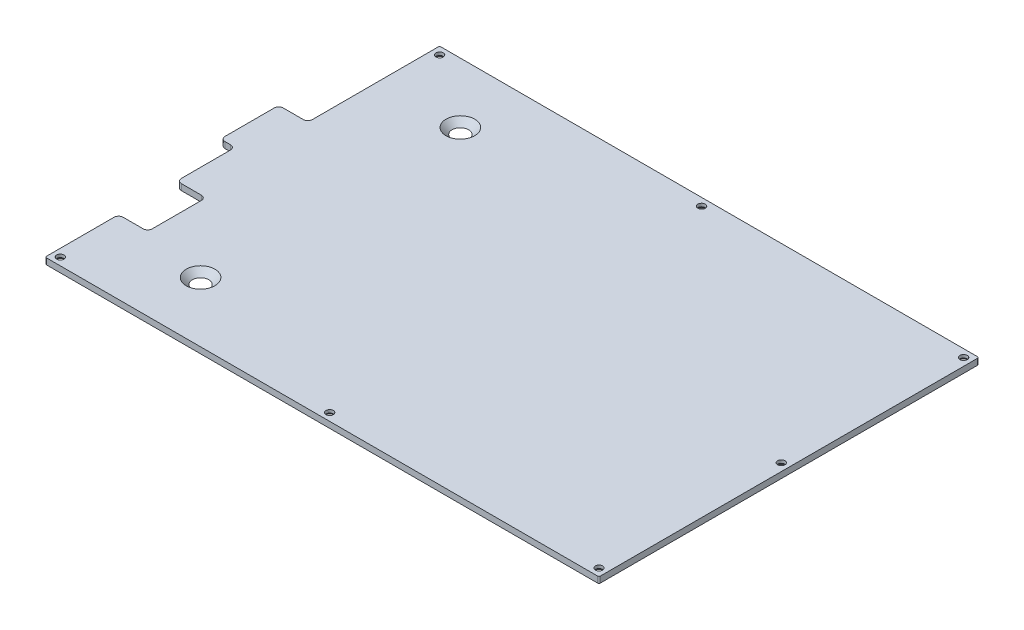
SolidWorks part; units mm, degrees
material "6061-T6 (SS)"
ref_plane "Front Plane" through (0, 0, 0) normal (0, 0, 1) x (1, 0, 0)
ref_plane "Top Plane" through (0, 0, 0) normal (0, 1, 0) x (1, 0, 0)
ref_plane "Right Plane" through (0, 0, 0) normal (1, 0, 0) x (0, 0, -1)
sketch "Sketch1" plane through (0, 0, 0) normal (0, 1, 0) x (1, 0, 0)
  line L0 (0, 0) -> (0, 124.3)
  line L1 (0, 124.3) -> (-176.45, 124.3)
  line L2 (-176.45, 124.3) -> (-176.45, 81.2)
  line L3 (-176.45, 81.2) -> (-185.975, 81.2)
  line L4 (-185.975, 81.2) -> (-185.975, 62.15)
  line L5 (-185.975, 62.15) -> (-181.2125, 62.15)
  line L6 (-181.2125, 62.15) -> (-181.2125, 43.1)
  line L7 (-181.2125, 43.1) -> (-171.6875, 43.1)
  line L8 (-171.6875, 43.1) -> (-171.6875, 24.05)
  line L9 (-171.6875, 24.05) -> (-181.2125, 24.05)
  line L10 (-181.2125, 24.05) -> (-181.2125, 0)
  line L11 (-181.2125, 0) -> (0, 0)
  dimension "D2" = 19.05
  dimension "D3" = 4.7625
  dimension "D4" = 9.525
  dimension "D6" = 176.45
  dimension "D7" = 9.525
  dimension "D5" = 43.1
  dimension "D1" = 24.05
extrude "Plate Frame" add sketch "Sketch1" along normal blind 2
sketch "Sketch2" plane through (0, 0, 0) normal (0, -1, 0) x (1, 0, 0)
  line L0 (-178.7125, -2.5) -> (-90.6063, -2.5) construction
  line L1 (-90.6063, -2.5) -> (-2.5, -2.5) construction
  line L2 (-2.5, -2.5) -> (-2.5, -62.15) construction
  line L3 (-2.5, -62.15) -> (-2.5, -121.8) construction
  line L4 (-2.5, -121.8) -> (-88.225, -121.8) construction
  line L5 (-88.225, -121.8) -> (-173.95, -121.8) construction
  line L6 (-181.2125, 0) -> (0, 0) construction
  line L7 (-181.2125, -24.05) -> (-181.2125, 0) construction
  line L8 (0, 0) -> (0, -124.3) construction
  line L9 (0, -124.3) -> (-176.45, -124.3) construction
  line L10 (-176.45, -124.3) -> (-176.45, -81.2) construction
  point P0 (-178.7125, -2.5)
  point P1 (-90.6063, -2.5)
  point P2 (-2.5, -2.5)
  point P3 (-2.5, -62.15)
  point P4 (-2.5, -121.8)
  point P5 (-88.225, -121.8)
  point P6 (-173.95, -121.8)
  dimension "D1" = 2.5
  dimension "D2" = 2.5
  dimension "D3" = 2.5
  dimension "D4" = 2.5
  dimension "D5" = 2.5
hole_wizard "CSK for M2 Flat Head Machine Screw1" positions "Sketch3" profile "Sketch4" countersink size "M2" standard "ANSI Metric" end condition through all
sketch "Sketch3" plane through (0, 0, 0) normal (0, -1, 0) x (-1, 0, 0)
  point P0 (178.7125, 2.5)
  point P3 (90.6063, 2.5)
  point P6 (2.5, 2.5)
  point P9 (2.5, 62.15)
  point P12 (2.5, 121.8)
  point P15 (88.225, 121.8)
  point P18 (173.95, 121.8)
sketch "Sketch4" plane through (-178.7125, 0, -2.5) normal (1, 0, 0) x (0, 0, -1)
  line L0 (0, 0) -> (0, 2)
  line L1 (0, 2) -> (1.2, 2)
  line L2 (1.2, 2) -> (1.2, 1)
  line L3 (1.2, 1) -> (2.2, 0)
  line L5 (2.2, 0) -> (0, 0)
  line L6 (-1.2, 1) -> (-2.2, 0) construction
  line L11 (0, -6.35) -> (0, 107.95) construction
  dimension "Thru Hole Dia." = 2.4
  dimension "Thru Hole Depth" = 2
  dimension "Near C'Sink Dia." = 4.4
  dimension "Near C'Sink Angle" = 90
sketch "Sketch5" plane through (0, 2, 0) normal (0, 1, 0) x (1, 0, 0)
  line L0 (-150, 104.65) -> (-150, 19.65) construction
  line L1 (-150, 62.15) -> (-2.5, 62.15) construction
  line L3 (0, 0) -> (0, 124.3) construction
  line L4 (-150, 104.65) -> (-25, 104.65) construction
  line L5 (-25, 104.65) -> (-25, 62.15) construction
  dimension "D1" = 85
  dimension "D2" = 150
  dimension "D3" = 25
hole_wizard "CSK for M4 Flat Head Machine Screw1" positions "Sketch6" profile "Sketch7" countersink size "M4" standard "ANSI Metric" end condition through all
sketch "Sketch6" plane through (0, 2, 0) normal (0, 1, 0) x (1, 0, 0)
  point P0 (-150, 104.65)
  point P3 (-150, 19.65)
sketch "Sketch7" plane through (-150, 2, -104.65) normal (1, 0, 0) x (0, 0, 1)
  line L0 (0, 0) -> (0, 2)
  line L1 (0, 2) -> (2.25, 2)
  line L2 (2.25, 2) -> (2.25, 2.45)
  line L3 (2.25, 2.45) -> (4.7, 0)
  line L5 (4.7, 0) -> (0, 0)
  line L6 (-2.25, 2.45) -> (-4.7, 0) construction
  line L11 (0, -6.35) -> (0, 107.95) construction
  dimension "Thru Hole Dia." = 4.5
  dimension "Thru Hole Depth" = 2
  dimension "Near C'Sink Dia." = 9.4
  dimension "Near C'Sink Angle" = 90
fillet "Fillet1" radius 1.5 8 edges at (-171.6875, 1, -24.05) (-181.2125, 1, -24.05) (-171.6875, 1, -43.1) (-181.2125, 1, -62.15) (-181.2125, 1, -43.1) (-185.975, 1, -62.15) (-185.975, 1, -81.2) (-176.45, 1, -81.2)
fillet "Fillet2" radius 0.5 4 edges at (-176.45, 1, -124.3) (-181.2125, 1, 0) (0, 1, -124.3) (0, 1, 0)
equation "\"D3@Sketch1\"=19.05/4"
equation "\"D4@Sketch1\"=19.05/2"
equation "\"D5@Sketch1\"=2*19.05 + 5"
equation "\"D1@Sketch1\"=19.05 + 5"
equation "\"D6@Sketch1\"=19.05*9 + 5"
